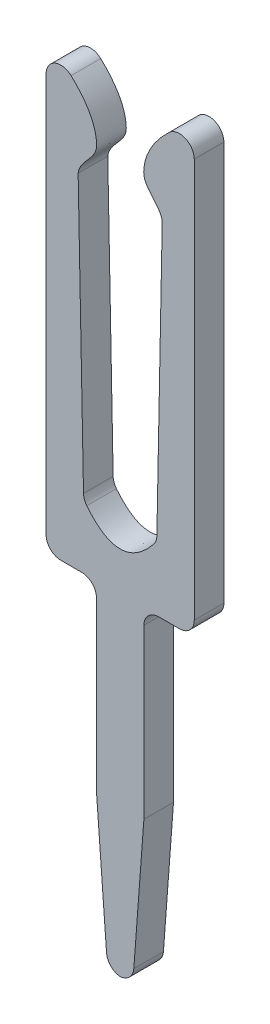
SolidWorks part; units mm, degrees
material "1060 Alloy"
ref_plane "Front Plane" through (0, 0, 0) normal (0, 0, 1) x (1, 0, 0)
ref_plane "Top Plane" through (0, 0, 0) normal (0, 1, 0) x (1, 0, 0)
ref_plane "Right Plane" through (0, 0, 0) normal (1, 0, 0) x (0, 0, -1)
sketch "Sketch1" plane through (0, 0, 0) normal (0, 0, 1) x (1, 0, 0)
  line L0 (-0.32, 1.9994) -> (-0.32, 4.2668)
  line L1 (-0.1839, 0.1844) -> (-0.32, 1.9994)
  line L2 (-0.5677, 9.1083) -> (-0.4952, 5.4017)
  line L3 (-1, 4.6668) -> (-1, 10.0572)
  line L4 (0.1839, 0.1844) -> (0.32, 1.9994)
  line L5 (0.32, 1.9994) -> (0.32, 4.2668)
  line L6 (0.52, 4.4668) -> (0.8, 4.4668)
  line L7 (1, 4.6668) -> (1, 10.0572)
  line L8 (0.5677, 9.1083) -> (0.4952, 5.4017)
  line L9 (-0.52, 4.4668) -> (-0.8, 4.4668)
  line L10 (0, 5) -> (0, 0) construction
  arc A0 (0, 0) -> (-0.1839, 0.1844) centre (0.0156, 0.1994) cw
  arc A1 (-0.4952, 5.4017) -> (-0.4511, 5.2802) centre (-0.2953, 5.4056) ccw
  arc A2 (-1, 10.0572) -> (-0.663, 10.2029) centre (-0.8, 10.0572) cw
  arc A3 (-0.8, 4.4668) -> (-1, 4.6668) centre (-0.8, 4.6668) cw
  arc A4 (0, 0) -> (0.1839, 0.1844) centre (-0.0156, 0.1994) ccw
  arc A5 (0.32, 4.2668) -> (0.52, 4.4668) centre (0.52, 4.2668) cw
  arc A6 (0.8, 4.4668) -> (1, 4.6668) centre (0.8, 4.6668) ccw
  arc A7 (1, 10.0572) -> (0.663, 10.2029) centre (0.8, 10.0572) ccw
  arc A8 (0.4952, 5.4017) -> (0.4511, 5.2802) centre (0.2953, 5.4056) cw
  arc A9 (-0.32, 4.2668) -> (-0.52, 4.4668) centre (-0.52, 4.2668) ccw
  spline S0 degree 3 poles (0.663, 10.2029) (0.4876, 10.0381) (0.3262, 9.8162) (0.3107, 9.3882) (0.5485, 9.276) (0.5677, 9.1083) knots 0.253308 0.253308 0.253308 0.253308 0.663172 0.707067 1 1 1 1
  spline S1 degree 2 poles (-0.4511, 5.2802) (0, 4.7198) (0.4511, 5.2802) knots 0.043405 0.043405 0.043405 0.956595 0.956595 0.956595
  spline S2 degree 3 poles (-0.663, 10.2029) (-0.4876, 10.0381) (-0.3262, 9.8162) (-0.3107, 9.3882) (-0.5485, 9.276) (-0.5677, 9.1083) knots 0.253308 0.253308 0.253308 0.253308 0.663172 0.707067 1 1 1 1
  dimension "D2" = 0.2
  dimension "D7" = 0.2
  dimension "D8" = 0.68
  dimension "D10" = 0.2
  dimension "D13" = 0.2
  dimension "D1" = 5
  dimension "D3" = 0.1839
  dimension "D4" = 1.815
  dimension "D5" = 0.64
  dimension "D9" = 5.3904
  dimension "D11" = 0.8134
  dimension "D12" = 0.1215
  dimension "D14" = 0.4323
  dimension "D15" = 0.337
  dimension "D16" = 0.9489
  dimension "D17" = 0.5048
extrude "Boss-Extrude1" add sketch "Sketch1" against normal mid plane 0.4
ref_axis "Axis1" through (0, 5, 0) along (0, -1, 0)
